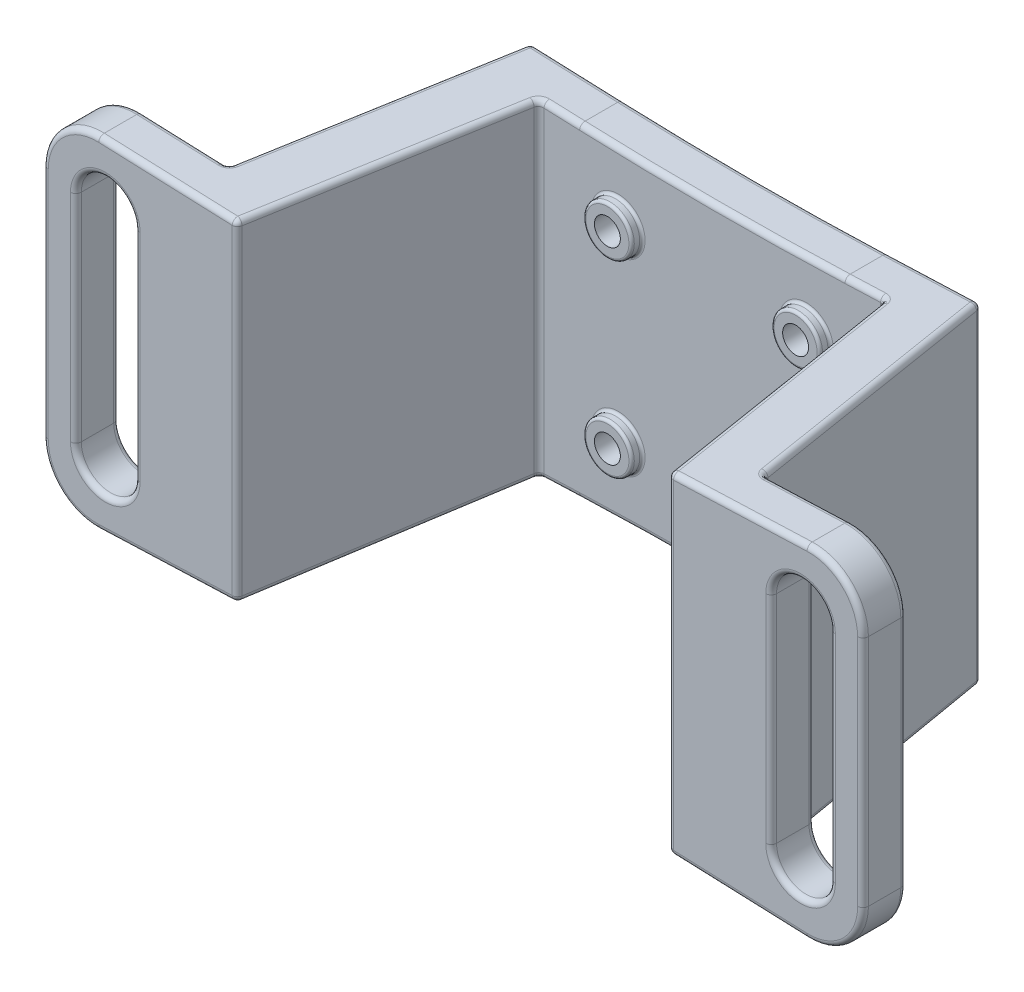
SolidWorks part; units mm, degrees
ref_plane "Front Plane" through (0, 0, 0) normal (0, 0, 1) x (1, 0, 0)
ref_plane "Top Plane" through (0, 0, 0) normal (0, 1, 0) x (1, 0, 0)
ref_plane "Right Plane" through (0, 0, 0) normal (1, 0, 0) x (0, 0, -1)
sketch "Sketch1" plane through (0, 0, 0) normal (0, 0, 1) x (1, 0, 0)
  line L0 (0, 0) -> (13.8229, 0) construction
  line L1 (13.8229, 0) -> (13.8229, -13.8229) construction
  line L2 (13.8229, -13.8229) -> (0, -13.8229) construction
  line L3 (0, -13.8229) -> (0, 0) construction
  line L4 (-18.6197, 1.026) -> (-18.6197, -14.849) construction
  line L5 (-18.6197, 1.026) -> (-18.6197, -14.849) construction
  line L6 (-16.4607, 1.026) -> (-16.4607, -14.849)
  line L7 (-20.7787, 1.026) -> (-20.7787, -14.849)
  line L8 (13.8229, 4.3686) -> (13.8229, 0) construction
  line L9 (-23.2063, 5.7885) -> (18.1915, 4.201)
  line L10 (-23.2063, 5.7885) -> (-23.2063, -19.6115)
  line L11 (-23.2063, -19.6115) -> (18.1915, -18.024)
  line L12 (18.1915, 4.201) -> (18.1915, -18.024)
  line L13 (-23.2063, 5.7885) -> (18.1915, -18.024) construction
  line L14 (-23.2063, -19.6115) -> (18.1915, 4.201) construction
  line L15 (13.8229, 0) -> (18.1915, 0) construction
  line L16 (-18.6197, 3.185) -> (-18.6197, 5.6126) construction
  line L17 (-20.7787, -6.9115) -> (-23.2063, -6.9115) construction
  line L18 (6.9115, 0) -> (6.9115, -13.8229) construction
  line L19 (0.4303, 0) -> (0.4303, -13.8229) construction
  line L20 (13.3927, 0) -> (13.3927, -13.8229) construction
  line L21 (34.6017, -6.9115) -> (37.0293, -6.9115) construction
  line L22 (32.4427, 3.185) -> (32.4427, 5.6126) construction
  line L23 (0, 0) -> (-4.3686, 0) construction
  line L24 (37.0293, -19.6115) -> (-4.3686, 4.201) construction
  line L25 (37.0293, 5.7885) -> (-4.3686, -18.024) construction
  line L26 (0, 4.3686) -> (0, 0) construction
  line L27 (32.4427, 1.026) -> (32.4427, -14.849) construction
  line L28 (13.8229, -13.8229) -> (13.8229, 0) construction
  line L29 (0, 0) -> (0, -13.8229) construction
  line L30 (-4.3686, 4.201) -> (-4.3686, -18.024)
  line L31 (37.0293, -19.6115) -> (-4.3686, -18.024)
  line L32 (37.0293, 5.7885) -> (37.0293, -19.6115)
  line L33 (37.0293, 5.7885) -> (-4.3686, 4.201)
  line L34 (32.4427, 1.026) -> (32.4427, -14.849) construction
  line L35 (30.2837, 1.026) -> (30.2837, -14.849)
  line L36 (34.6017, 1.026) -> (34.6017, -14.849)
  circle A0 centre (0, 0) radius 1.905
  circle A1 centre (13.8229, 0) radius 1.905
  circle A2 centre (13.8229, -13.8229) radius 1.905
  circle A3 centre (0, -13.8229) radius 1.905
  arc A4 (-16.4607, 1.026) -> (-20.7787, 1.026) centre (-18.6197, 1.026) ccw
  arc A5 (-20.7787, -14.849) -> (-16.4607, -14.849) centre (-18.6197, -14.849) ccw
  circle A6 centre (13.8229, -13.8229) radius 1.905
  circle A7 centre (0, -13.8229) radius 1.905
  circle A8 centre (0, 0) radius 1.905
  circle A9 centre (13.8229, 0) radius 1.905
  arc A10 (30.2837, 1.026) -> (34.6017, 1.026) centre (32.4427, 1.026) cw
  arc A11 (34.6017, -14.849) -> (30.2837, -14.849) centre (32.4427, -14.849) cw
  point P11 (-18.6197, -6.9115)
  point P12 (-18.6197, -6.9115)
  point P13 (0, -6.9115)
  point P18 (-1.1275, -6.9115)
  point P51 (14.9504, -6.9115)
  point P52 (32.4427, -6.9115)
  dimension "D2" = 3.81
  dimension "D5" = 2.159
  dimension "D1" = 13.8229
  dimension "D3" = 15.875
  dimension "D4" = 6.4812
  dimension "D6" = 22.225
  dimension "D7" = 25.4
  dimension "D8" = 19.05
extrude "Boss-Extrude1" add sketch "Sketch1" along normal blind 3.175 contours L9 L33 L30 L31 L11 L12 A3 A2 A1 A0 | L33 L9 L10 L11 L31 L30 A5 L7 A4 L6 | L32 L33 L9 L12 L11 L31 L36 A11 L35 A10
fillet "Fillet1" radius 3.9688 4 edges at (-23.2063, -19.6115, 1.5875) (-23.2063, 5.7885, 1.5875) (37.0293, 5.7885, 1.5875) (37.0293, -19.6115, 1.5875)
sketch "Sketch2" plane through (0, 0, 3.175) normal (0, 0, 1) x (1, 0, 0)
  circle A12 centre (13.8229, 0) radius 1.905 construction
  circle A13 centre (13.8229, -13.8229) radius 1.905 construction
  circle A14 centre (0, -13.8229) radius 1.905 construction
  circle A15 centre (0, 0) radius 1.905 construction
  circle A16 centre (13.8229, 0) radius 1.905
  circle A17 centre (13.8229, -13.8229) radius 1.905
  circle A18 centre (0, -13.8229) radius 1.905
  circle A19 centre (0, 0) radius 1.905
  circle A20 centre (0, 0) radius 0.9525
  circle A21 centre (0, -13.8229) radius 0.9525
  circle A22 centre (13.8229, 0) radius 0.9525
  circle A23 centre (13.8229, -13.8229) radius 0.9525
  dimension "D1" = 1.905
extrude "Boss-Extrude2" add sketch "Sketch2" against normal blind 1.5875 contours A16 A23 | A19 A20 | A18 A21 | A17 A22
sketch "Sketch4" plane through (0, 0, 3.175) normal (0, 0, 1) x (1, 0, 0)
  circle A0 centre (0, 0) radius 1.778
  circle A1 centre (0, -13.8229) radius 1.778
  circle A2 centre (13.8229, 0) radius 1.778
  circle A3 centre (13.8229, -13.8229) radius 1.778
  circle A4 centre (13.8229, -13.8229) radius 0.9525 construction
  circle A5 centre (13.8229, 0) radius 0.9525 construction
  circle A6 centre (0, -13.8229) radius 0.9525 construction
  circle A7 centre (0, 0) radius 0.9525 construction
  circle A8 centre (13.8229, -13.8229) radius 0.9525
  circle A9 centre (13.8229, 0) radius 0.9525
  circle A10 centre (0, -13.8229) radius 0.9525
  circle A11 centre (0, 0) radius 0.9525
  dimension "D1" = 3.556
extrude "Boss-Extrude3" add sketch "Sketch4" along normal blind 0.7937 contours A3 | A8 | A11 | A0 | A10 | A1 | A9 | A2
sketch "Sketch5" plane through (0, 0, 3.175) normal (0, 0, -1) x (-1, 0, 0)
  line L1 (-19.6115, -18.9435) -> (-19.6115, 5.1206)
  line L2 (5.7885, -18.9435) -> (5.7885, 5.1206)
  line L3 (-34.6017, 1.026) -> (-34.6017, -14.849)
  line L4 (-30.2837, -14.849) -> (-30.2837, 1.026)
  line L8 (-34.6017, 1.026) -> (-34.6017, -14.849)
  line L9 (-30.2837, -14.849) -> (-30.2837, 1.026)
  line L20 (20.7787, -14.849) -> (20.7787, 1.026)
  line L21 (16.4607, 1.026) -> (16.4607, -14.849)
  line L22 (20.7787, -14.849) -> (20.7787, 1.026)
  line L23 (16.4607, 1.026) -> (16.4607, -14.849)
  line L28 (23.2063, -15.4876) -> (23.2063, 1.6647)
  line L29 (-6.9115, -18.4565) -> (19.0855, -19.4534)
  line L30 (-32.9084, -19.4534) -> (-6.9115, -18.4565)
  line L31 (-37.0293, 1.6647) -> (-37.0293, -15.4876)
  line L32 (-6.9115, 4.6336) -> (-32.9084, 5.6305)
  line L33 (19.0855, 5.6305) -> (-6.9115, 4.6336)
  line L34 (23.2063, -15.4876) -> (23.2063, 1.6647)
  line L35 (-6.9115, -18.4565) -> (19.0855, -19.4534)
  line L36 (-32.9084, -19.4534) -> (-6.9115, -18.4565)
  line L37 (-37.0293, 1.6647) -> (-37.0293, -15.4876)
  line L38 (-6.9115, 4.6336) -> (-32.9084, 5.6305)
  line L39 (19.0855, 5.6305) -> (-6.9115, 4.6336)
  arc A2 (-34.6017, -14.849) -> (-30.2837, -14.849) centre (-32.4427, -14.849) ccw
  arc A3 (-30.2837, 1.026) -> (-34.6017, 1.026) centre (-32.4427, 1.026) ccw
  arc A4 (-34.6017, -14.849) -> (-30.2837, -14.849) centre (-32.4427, -14.849) ccw
  arc A5 (-30.2837, 1.026) -> (-34.6017, 1.026) centre (-32.4427, 1.026) ccw
  arc A6 (16.4607, -14.849) -> (20.7787, -14.849) centre (18.6197, -14.849) ccw
  arc A7 (20.7787, 1.026) -> (16.4607, 1.026) centre (18.6197, 1.026) ccw
  arc A8 (16.4607, -14.849) -> (20.7787, -14.849) centre (18.6197, -14.849) ccw
  arc A9 (20.7787, 1.026) -> (16.4607, 1.026) centre (18.6197, 1.026) ccw
  arc A14 (19.0855, -19.4534) -> (23.2063, -15.4876) centre (19.2376, -15.4876) ccw
  arc A15 (-37.0293, -15.4876) -> (-32.9084, -19.4534) centre (-33.0605, -15.4876) ccw
  arc A16 (-32.9084, 5.6305) -> (-37.0293, 1.6647) centre (-33.0605, 1.6647) ccw
  arc A17 (23.2063, 1.6647) -> (19.0855, 5.6305) centre (19.2376, 1.6647) ccw
  arc A18 (19.0855, -19.4534) -> (23.2063, -15.4876) centre (19.2376, -15.4876) ccw
  arc A19 (-37.0293, -15.4876) -> (-32.9084, -19.4534) centre (-33.0605, -15.4876) ccw
  arc A20 (-32.9084, 5.6305) -> (-37.0293, 1.6647) centre (-33.0605, 1.6647) ccw
  arc A21 (23.2063, 1.6647) -> (19.0855, 5.6305) centre (19.2376, 1.6647) ccw
  dimension "D1" = 0
  dimension "D4" = 12.7
  dimension "D5" = 12.7
  dimension "D2" = 0
  dimension "D3" = 0
extrude "Boss-Extrude4" add sketch "Sketch5" against normal blind 19.05
sketch "Sketch6" plane through (0, 0, 0) normal (0, 0, 1) x (1, 0, 0)
  line L1 (19.6115, -18.9435) -> (19.6115, 5.1206) construction
  line L2 (-19.0855, -19.4534) -> (6.9115, -18.4565) construction
  line L10 (-12.7735, -19.2114) -> (-12.7735, 5.3885)
  line L21 (-19.0855, 5.6305) -> (6.9115, 4.6336) construction
  line L22 (-16.4607, -14.849) -> (-16.4607, 1.026)
  line L23 (-20.7787, 1.026) -> (-20.7787, -14.849)
  line L24 (-16.4607, -14.849) -> (-16.4607, 1.026)
  line L25 (-20.7787, 1.026) -> (-20.7787, -14.849)
  line L26 (34.6017, -14.849) -> (34.6017, 1.026)
  line L27 (30.2837, 1.026) -> (30.2837, -14.849)
  line L28 (34.6017, -14.849) -> (34.6017, 1.026)
  line L29 (30.2837, 1.026) -> (30.2837, -14.849)
  line L30 (-5.7885, -18.9435) -> (-5.7885, 5.1206) construction
  line L31 (26.5965, -19.2114) -> (26.5965, 5.3885)
  line L32 (32.9084, -19.4534) -> (6.9115, -18.4565) construction
  line L33 (32.9084, 5.6305) -> (6.9115, 4.6336) construction
  line L35 (-19.0855, -19.4534) -> (6.9115, -18.4565)
  line L36 (-23.2063, 1.6647) -> (-23.2063, -15.4876)
  line L37 (6.9115, 4.6336) -> (-19.0855, 5.6305)
  line L38 (32.9084, 5.6305) -> (6.9115, 4.6336)
  line L39 (37.0293, -15.4876) -> (37.0293, 1.6647)
  line L40 (6.9115, -18.4565) -> (32.9084, -19.4534)
  line L41 (-19.0855, -19.4534) -> (6.9115, -18.4565)
  line L42 (-23.2063, 1.6647) -> (-23.2063, -15.4876)
  line L43 (6.9115, 4.6336) -> (-19.0855, 5.6305)
  line L44 (32.9084, 5.6305) -> (6.9115, 4.6336)
  line L45 (37.0293, -15.4876) -> (37.0293, 1.6647)
  line L46 (6.9115, -18.4565) -> (32.9084, -19.4534)
  circle A16 centre (0, -13.8229) radius 1.905
  circle A17 centre (0, -13.8229) radius 1.905
  circle A18 centre (13.8229, -13.8229) radius 1.905
  circle A19 centre (13.8229, -13.8229) radius 1.905
  circle A20 centre (13.8229, 0) radius 1.905
  circle A21 centre (13.8229, 0) radius 1.905
  circle A22 centre (0, 0) radius 1.905
  circle A23 centre (0, 0) radius 1.905
  arc A25 (-20.7787, -14.849) -> (-16.4607, -14.849) centre (-18.6197, -14.849) ccw
  arc A26 (-16.4607, 1.026) -> (-20.7787, 1.026) centre (-18.6197, 1.026) ccw
  arc A27 (-20.7787, -14.849) -> (-16.4607, -14.849) centre (-18.6197, -14.849) ccw
  arc A28 (-16.4607, 1.026) -> (-20.7787, 1.026) centre (-18.6197, 1.026) ccw
  arc A29 (34.6017, 1.026) -> (30.2837, 1.026) centre (32.4427, 1.026) ccw
  arc A30 (30.2837, -14.849) -> (34.6017, -14.849) centre (32.4427, -14.849) ccw
  arc A31 (34.6017, 1.026) -> (30.2837, 1.026) centre (32.4427, 1.026) ccw
  arc A32 (30.2837, -14.849) -> (34.6017, -14.849) centre (32.4427, -14.849) ccw
  arc A35 (-23.2063, -15.4876) -> (-19.0855, -19.4534) centre (-19.2376, -15.4876) ccw
  arc A36 (-19.0855, 5.6305) -> (-23.2063, 1.6647) centre (-19.2376, 1.6647) ccw
  arc A37 (37.0293, 1.6647) -> (32.9084, 5.6305) centre (33.0605, 1.6647) ccw
  arc A38 (32.9084, -19.4534) -> (37.0293, -15.4876) centre (33.0605, -15.4876) ccw
  arc A39 (-23.2063, -15.4876) -> (-19.0855, -19.4534) centre (-19.2376, -15.4876) ccw
  arc A40 (-19.0855, 5.6305) -> (-23.2063, 1.6647) centre (-19.2376, 1.6647) ccw
  arc A41 (37.0293, 1.6647) -> (32.9084, 5.6305) centre (33.0605, 1.6647) ccw
  arc A42 (32.9084, -19.4534) -> (37.0293, -15.4876) centre (33.0605, -15.4876) ccw
  point P36 (23.4581, 5.3109)
  point P41 (-9.5979, -19.1324)
  dimension "D2" = 0
  dimension "D1" = 0
  dimension "D7" = 6.985
  dimension "D8" = 6.985
  dimension "D3" = 0
  dimension "D4" = 0
  dimension "D5" = 0
  dimension "D6" = 0
  dimension "D9" = 0
extrude "Cut-Extrude1" cut sketch "Sketch6" along normal blind 19.05 contours A40 L43 L10 L41 A39 L42 L24 A28 L25 A27 | A42 L46 L31 L44 A41 L45 L29 A32 L28 A31
chamfer "Chamfer1" distance 19.05 distance2 3.175 1 edges at (-12.7735, -6.9115, 0)
chamfer "Chamfer4" distance 3.175 distance2 19.05 1 edges at (26.5965, -6.9115, 0)
chamfer "Chamfer2" distance 3.175 distance2 19.05 1 edges at (19.6115, -6.9115, 22.225)
chamfer "Chamfer3" distance 19.05 distance2 3.175 1 edges at (-5.7885, -6.9115, 22.225)
fillet "Fillet2" radius 0.1984 16 edges at (15.7279, -13.8229, 1.5875) (15.7279, -13.8229, 0) (15.6009, 0, 3.9688) (15.6009, 0, 3.175) (1.778, -13.8229, 3.9688) (1.778, -13.8229, 3.175) (1.778, 0, 3.9688) (1.778, 0, 3.175) (15.6009, -13.8229, 3.9688) (15.6009, -13.8229, 3.175) (15.7279, 0, 0) (15.7279, 0, 1.5875) (1.905, 0, 0) (1.905, 0, 1.5875) (1.905, -13.8229, 0) (1.905, -13.8229, 1.5875)
fillet "Fillet4" radius 254 2 edges at (6.9115, 4.6336, 1.5875) (6.9115, -18.4565, 1.5875)
fillet "Fillet3" radius 0.3969 64 edges at (18.128, -18.8867, 3.175) (-4.3051, -18.8867, 3.175) (-4.3051, 5.0637, 3.175) (18.128, 5.0637, 3.175) (35.8126, -18.3472, 22.225) (37.0293, -6.9115, 22.225) (35.8126, 4.5243, 22.225) (27.8475, 5.4364, 22.225) (32.4427, 3.185, 22.225) (34.6017, -6.9115, 22.225) (32.4427, -17.008, 22.225) (30.2837, -6.9115, 22.225) (19.6115, -6.9115, 3.175) (-5.7885, -6.9115, 3.175) (-16.4607, -6.9115, 22.225) (-18.6197, -17.008, 22.225) (-20.7787, -6.9115, 22.225) (-18.6197, 3.185, 22.225) (-14.0245, -19.2594, 22.225) (-21.9896, 4.5243, 22.225) (-23.2063, -6.9115, 22.225) (-21.9896, -18.3472, 22.225) (-20.7787, -6.9115, 19.05) (-18.6197, 3.185, 19.05) (-16.4607, -6.9115, 19.05) (-15.9295, 5.5095, 19.05) (-21.9896, 4.5243, 19.05) (-23.2063, -6.9115, 19.05) (-21.9896, -18.3472, 19.05) (-15.9295, -19.3324, 19.05) (-18.6197, -17.008, 19.05) (-12.7735, -6.9115, 19.05) (29.7525, -19.3324, 19.05) (35.8126, -18.3472, 19.05) (37.0293, -6.9115, 19.05) (35.8126, 4.5243, 19.05) (29.7525, 5.5095, 19.05) (32.4427, -17.008, 19.05) (30.2837, -6.9115, 19.05) (32.4427, 3.185, 19.05) (34.6017, -6.9115, 19.05) (26.5965, -6.9115, 19.05) (-6.2101, 5.1368, 0) (-6.2101, -18.9597, 0) (-9.5985, -6.9115, 0) (-11.186, 5.3276, 9.525) (-11.186, -19.1505, 9.525) (20.033, 5.1368, 0) (25.009, 5.3276, 9.525) (20.033, -18.9597, 0) (23.4215, -6.9115, 0) (25.009, -19.1505, 9.525) (21.199, 5.1815, 12.7) (27.8475, -19.2594, 22.225) (22.7865, -6.9115, 22.225) (21.199, -19.0044, 12.7) (-14.0245, 5.4364, 22.225) (-8.9635, -6.9115, 22.225) (-7.376, 5.1815, 12.7) (-7.376, -19.0044, 12.7) (6.9115, 4.8203, 0) (6.9115, 4.8203, 3.175) (6.9115, -18.6432, 0) (6.9115, -18.6432, 3.175)
